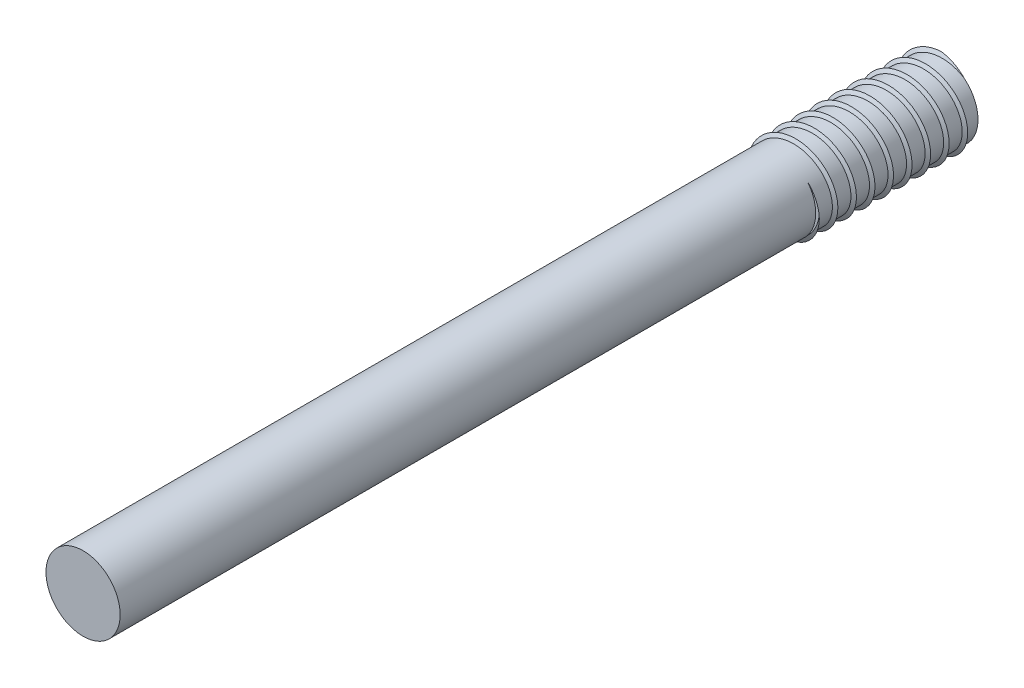
SolidWorks part; units mm, degrees
ref_plane "Front Plane" through (0, 0, 0) normal (0, 0, 1) x (1, 0, 0)
ref_plane "Top Plane" through (0, 0, 0) normal (0, 1, 0) x (1, 0, 0)
ref_plane "Right Plane" through (0, 0, 0) normal (1, 0, 0) x (0, 0, -1)
sketch "Sketch1" plane through (0, 0, 0) normal (0, 0, 1) x (1, 0, 0)
  line L0 (-5, 10) -> (-5, 0)
  line L1 (-5, -10) -> (5, -10)
  line L2 (-5, -10) -> (-5, 10)
  line L3 (-5, 10) -> (5, 10)
  line L4 (5, -10) -> (5, 10)
  line L5 (-5, -10) -> (5, 10) construction
  line L6 (-5, 10) -> (5, -10) construction
  circle A0 centre (0, 5) radius 2.5
  circle A1 centre (0, 5) radius 10
  point P0 (0, 0)
  dimension "D1" = 10
  dimension "D2" = 20
extrude "Boss-Extrude1" add sketch "Sketch1" along normal blind 5 contours L2 A1 L4 L3 L0 A0 | A1 L2 L1 L4 region at (0, 2.355, 0) region at (0, -7.2687, 0)
extrude "Boss-Extrude2" add sketch "Sketch1<3>" against normal blind 50 contours L4 A1 L2 L0 L3 | L2 A1 L4 L3 L0 A0 region at (0, 2.355, 0) region at (-5.2735, 5, 0)
sketch "Sketch1<3>" plane through (0, 0, 0) normal (0, 0, 1) x (1, 0, 0) same geometry as "Sketch1"
sketch "Sketch2" plane through (0, 0, -50) normal (0, 0, -1) x (-1, 0, 0)
  circle A0 centre (0, 5) radius 8
extrude "Cut-Extrude1" cut sketch "Sketch2" against normal blind 50
sketch "Sketch3" plane through (0, 0, -50) normal (0, 0, -1) x (-1, 0, 0)
  circle A0 centre (0, 5) radius 8
curve "Helix/Spiral1" pitch 4 height 140 radius 8 centre (0, 5, -50) axis (0, 0, 1) start towards (-1, 0, 0)
ref_plane "Plane1" through (0, 5, 0) normal (0, 1, 0) x (1, 0, 0)
sketch "Sketch4" plane through (0, 5, 0) normal (0, 1, 0) x (1, 0, 0)
  line L2 (-8.75, 50) -> (-8, 49.567)
  line L3 (-8, 49.567) -> (-8, 50.433)
  line L4 (-8, 50.433) -> (-8.75, 50)
  circle A0 centre (-8.25, 50) radius 0.25 construction
sweep "Cut-Sweep1" cut profiles "Sketch4" path "Helix/Spiral1" align with end faces yes
sketch "Sketch6" plane through (0, 10, 0) normal (0, 1, 0) x (1, 0, 0)
  line L1 (-5, -5) -> (5, -5)
  line L2 (-5, -5) -> (-5, 0)
  line L3 (-5, 0) -> (5, 0)
  line L4 (5, -5) -> (5, 0)
extrude "Cut-Extrude2" cut sketch "Sketch6" against normal blind 48
ref_plane "Plane2" through (0, 0, -45) normal (0, 0, -1) x (-1, 0, 0)
sketch "Sketch7" plane through (0, 0, -45) normal (0, 0, -1) x (-1, 0, 0)
  line L0 (0.8292, 14.2128) -> (1.3216, 14.9123)
  line L1 (0.4696, 14.989) -> (0.8292, 14.2128)
  line L2 (0, 14.25) -> (0.4277, 14.9908)
  line L4 (-0.4277, 14.9908) -> (0, 14.25)
  line L5 (0.433, 15) -> (0, 15) [skipped]
  line L6 (1.6517, 14.1013) -> (2.2048, 14.7539)
  line L7 (1.3631, 14.9067) -> (1.6517, 14.1013)
  line L8 (2.4608, 13.9167) -> (3.0702, 14.517)
  line L9 (2.2456, 14.7446) -> (2.4608, 13.9167)
  line L10 (3.2502, 13.6602) -> (3.911, 14.2035)
  line L11 (3.1101, 14.5041) -> (3.2502, 13.6602)
  line L12 (4.0134, 13.334) -> (4.7202, 13.8159)
  line L13 (3.9495, 14.187) -> (4.0134, 13.334)
  line L14 (4.7443, 12.9407) -> (5.4915, 13.3572)
  line L15 (4.7571, 13.796) -> (4.7443, 12.9407)
  line L16 (5.437, 12.4834) -> (6.2185, 12.8314)
  line L17 (5.5264, 13.3342) -> (5.437, 12.4834)
  line L18 (6.0859, 11.9659) -> (6.8955, 12.2424)
  line L19 (6.2513, 12.8052) -> (6.0859, 11.9659)
  line L20 (6.6859, 11.3923) -> (7.5169, 11.5951)
  line L21 (6.9257, 12.2135) -> (6.6859, 11.3923)
  line L22 (7.2319, 10.7673) -> (8.0778, 10.8948)
  line L23 (7.5445, 11.5636) -> (7.2319, 10.7673)
  line L24 (7.7198, 10.0958) -> (8.5737, 10.147)
  line L25 (8.1025, 10.8609) -> (7.7198, 10.0958)
  line L26 (8.1455, 9.3833) -> (9.0006, 9.3577)
  line L27 (8.5952, 10.111) -> (8.1455, 9.3833)
  line L28 (8.5056, 8.6355) -> (9.355, 8.5333)
  line L29 (9.0188, 9.32) -> (8.5056, 8.6355)
  line L30 (8.7973, 7.8584) -> (9.634, 7.6805)
  line L31 (9.3697, 8.4941) -> (8.7973, 7.8584)
  line L32 (9.0181, 7.0583) -> (9.8355, 6.8062)
  line L33 (9.6452, 7.6402) -> (9.0181, 7.0583)
  line L34 (9.1663, 6.2417) -> (9.9578, 5.9172)
  line L35 (9.843, 6.765) -> (9.1663, 6.2417)
  line L36 (9.2407, 5.415) -> (10, 5.0209)
  line L37 (9.9616, 5.8755) -> (9.2407, 5.415)
  line L38 (9.2407, 4.585) -> (9.9616, 4.1245)
  line L39 (10, 4.9791) -> (9.2407, 4.585)
  line L40 (9.1663, 3.7583) -> (9.843, 3.235)
  line L41 (9.9578, 4.0828) -> (9.1663, 3.7583)
  line L42 (9.0181, 2.9417) -> (9.6452, 2.3598)
  line L43 (9.8355, 3.1938) -> (9.0181, 2.9417)
  line L44 (8.7973, 2.1416) -> (9.3697, 1.5059)
  line L45 (9.634, 2.3195) -> (8.7973, 2.1416)
  line L46 (8.5056, 1.3645) -> (9.0188, 0.68)
  line L47 (9.355, 1.4667) -> (8.5056, 1.3645)
  line L48 (8.1455, 0.6167) -> (8.5952, -0.111)
  line L49 (9.0006, 0.6423) -> (8.1455, 0.6167)
  line L50 (7.7198, -0.0958) -> (8.1025, -0.8609)
  line L51 (8.5737, -0.147) -> (7.7198, -0.0958)
  line L52 (7.2319, -0.7673) -> (7.5445, -1.5636)
  line L53 (8.0778, -0.8948) -> (7.2319, -0.7673)
  line L54 (6.6859, -1.3923) -> (6.9257, -2.2135)
  line L55 (7.5169, -1.5951) -> (6.6859, -1.3923)
  line L56 (6.0859, -1.9659) -> (6.2513, -2.8052)
  line L57 (6.8955, -2.2424) -> (6.0859, -1.9659)
  line L58 (5.437, -2.4834) -> (5.5264, -3.3342)
  line L59 (6.2185, -2.8314) -> (5.437, -2.4834)
  line L60 (4.7443, -2.9407) -> (4.7571, -3.796)
  line L61 (5.4915, -3.3572) -> (4.7443, -2.9407)
  line L62 (4.0134, -3.334) -> (3.9495, -4.187)
  line L63 (4.7202, -3.8159) -> (4.0134, -3.334)
  line L64 (3.2502, -3.6602) -> (3.1101, -4.5041)
  line L65 (3.911, -4.2035) -> (3.2502, -3.6602)
  line L66 (2.4608, -3.9167) -> (2.2456, -4.7446)
  line L67 (3.0702, -4.517) -> (2.4608, -3.9167)
  line L68 (1.6517, -4.1013) -> (1.3631, -4.9067)
  line L69 (2.2048, -4.7539) -> (1.6517, -4.1013)
  line L70 (0.8292, -4.2128) -> (0.4696, -4.989)
  line L71 (1.3216, -4.9123) -> (0.8292, -4.2128)
  line L72 (0, -4.25) -> (-0.4277, -4.9908)
  line L73 (0.4277, -4.9908) -> (0, -4.25)
  line L74 (-0.8292, -4.2128) -> (-1.3216, -4.9123)
  line L75 (-0.4696, -4.989) -> (-0.8292, -4.2128)
  line L76 (-1.6517, -4.1013) -> (-2.2048, -4.7539)
  line L77 (-1.3631, -4.9067) -> (-1.6517, -4.1013)
  line L78 (-2.4608, -3.9167) -> (-3.0702, -4.517)
  line L79 (-2.2456, -4.7446) -> (-2.4608, -3.9167)
  line L80 (-3.2502, -3.6602) -> (-3.911, -4.2035)
  line L81 (-3.1101, -4.5041) -> (-3.2502, -3.6602)
  line L82 (-4.0134, -3.334) -> (-4.7202, -3.8159)
  line L83 (-3.9495, -4.187) -> (-4.0134, -3.334)
  line L84 (-4.7443, -2.9407) -> (-5.4915, -3.3572)
  line L85 (-4.7571, -3.796) -> (-4.7443, -2.9407)
  line L86 (-5.437, -2.4834) -> (-6.2185, -2.8314)
  line L87 (-5.5264, -3.3342) -> (-5.437, -2.4834)
  line L88 (-6.0859, -1.9659) -> (-6.8955, -2.2424)
  line L89 (-6.2513, -2.8052) -> (-6.0859, -1.9659)
  line L90 (-6.6859, -1.3923) -> (-7.5169, -1.5951)
  line L91 (-6.9257, -2.2135) -> (-6.6859, -1.3923)
  line L92 (-7.2319, -0.7673) -> (-8.0778, -0.8948)
  line L93 (-7.5445, -1.5636) -> (-7.2319, -0.7673)
  line L94 (-7.7198, -0.0958) -> (-8.5737, -0.147)
  line L95 (-8.1025, -0.8609) -> (-7.7198, -0.0958)
  line L96 (-8.1455, 0.6167) -> (-9.0006, 0.6423)
  line L97 (-8.5952, -0.111) -> (-8.1455, 0.6167)
  line L98 (-8.5056, 1.3645) -> (-9.355, 1.4667)
  line L99 (-9.0188, 0.68) -> (-8.5056, 1.3645)
  line L100 (-8.7973, 2.1416) -> (-9.634, 2.3195)
  line L101 (-9.3697, 1.5059) -> (-8.7973, 2.1416)
  line L102 (-9.0181, 2.9417) -> (-9.8355, 3.1938)
  line L103 (-9.6452, 2.3598) -> (-9.0181, 2.9417)
  line L104 (-9.1663, 3.7583) -> (-9.9578, 4.0828)
  line L105 (-9.843, 3.235) -> (-9.1663, 3.7583)
  line L106 (-9.2407, 4.585) -> (-10, 4.9791)
  line L107 (-9.9616, 4.1245) -> (-9.2407, 4.585)
  line L108 (-9.2407, 5.415) -> (-9.9616, 5.8755)
  line L109 (-10, 5.0209) -> (-9.2407, 5.415)
  line L110 (-9.1663, 6.2417) -> (-9.843, 6.765)
  line L111 (-9.9578, 5.9172) -> (-9.1663, 6.2417)
  line L112 (-9.0181, 7.0583) -> (-9.6452, 7.6402)
  line L113 (-9.8355, 6.8062) -> (-9.0181, 7.0583)
  line L114 (-8.7973, 7.8584) -> (-9.3697, 8.4941)
  line L115 (-9.634, 7.6805) -> (-8.7973, 7.8584)
  line L116 (-8.5056, 8.6355) -> (-9.0188, 9.32)
  line L117 (-9.355, 8.5333) -> (-8.5056, 8.6355)
  line L118 (-8.1455, 9.3833) -> (-8.5952, 10.111)
  line L119 (-9.0006, 9.3577) -> (-8.1455, 9.3833)
  line L120 (-7.7198, 10.0958) -> (-8.1025, 10.8609)
  line L121 (-8.5737, 10.147) -> (-7.7198, 10.0958)
  line L122 (-7.2319, 10.7673) -> (-7.5445, 11.5636)
  line L123 (-8.0778, 10.8948) -> (-7.2319, 10.7673)
  line L124 (-6.6859, 11.3923) -> (-6.9257, 12.2135)
  line L125 (-7.5169, 11.5951) -> (-6.6859, 11.3923)
  line L126 (-6.0859, 11.9659) -> (-6.2513, 12.8052)
  line L127 (-6.8955, 12.2424) -> (-6.0859, 11.9659)
  line L128 (-5.437, 12.4834) -> (-5.5264, 13.3342)
  line L129 (-6.2185, 12.8314) -> (-5.437, 12.4834)
  line L130 (-4.7443, 12.9407) -> (-4.7571, 13.796)
  line L131 (-5.4915, 13.3572) -> (-4.7443, 12.9407)
  line L132 (-4.0134, 13.334) -> (-3.9495, 14.187)
  line L133 (-4.7202, 13.8159) -> (-4.0134, 13.334)
  line L134 (-3.2502, 13.6602) -> (-3.1101, 14.5041)
  line L135 (-3.911, 14.2035) -> (-3.2502, 13.6602)
  line L136 (-2.4608, 13.9167) -> (-2.2456, 14.7446)
  line L137 (-3.0702, 14.517) -> (-2.4608, 13.9167)
  line L138 (-1.6517, 14.1013) -> (-1.3631, 14.9067)
  line L139 (-2.2048, 14.7539) -> (-1.6517, 14.1013)
  line L140 (-0.8292, 14.2128) -> (-0.4696, 14.989)
  line L141 (-1.3216, 14.9123) -> (-0.8292, 14.2128)
  circle A0 centre (0, 5) radius 10
  circle A1 centre (0, 5) radius 12.0427
  point P218 (0, 5)
  dimension "D1" = 70
extrude "Cut-Extrude3" cut sketch "Sketch7" against normal blind 10 contours L134 A0 L135 | L136 A0 L137 | L138 A0 L139 | L140 A0 L141 | L2 A0 L4 | L0 A0 L1 | L6 A0 L7 | L8 A0 L9 | L10 A0 L11 | L132 A0 L133 | L130 A0 L131 | L128 A0 L129 | L126 A0 L127 | L124 A0 L125 | L122 A0 L123 | L120 A0 L121 | L118 A0 L119 | L12 A0 L13 | L14 A0 L15 | L16 A0 L17 | L116 A0 L117 region at (-0.8738, 14.7087, -45) region at (-1.7406, 14.5913, -45) region at (0, 14.748, -45) region at (-2.5933, 14.3967, -45) region at (0.8738, 14.7087, -45) region at (-3.4252, 14.1264, -45) region at (1.7406, 14.5913, -45) region at (-4.2295, 13.7826, -45) region at (2.5933, 14.3967, -45) region at (-4.9997, 13.3681, -45) region at (3.4252, 14.1264, -45) region at (-5.7297, 12.8863, -45) region at (4.2295, 13.7826, -45) region at (4.9997, 13.3681, -45) region at (5.7297, 12.8863, -45) region at (6.4136, 12.3409, -45) region at (7.0458, 11.7365, -45) region at (7.6213, 11.0778, -45) region at (8.1354, 10.3701, -45) region at (8.584, 9.6193, -45) region at (8.9635, 8.8312, -45)
extrude "Cut-Extrude4" cut sketch "Sketch7<8>" against normal blind 10 contours L114 A0 L115 | L112 A0 L113 | L110 A0 L111 | L108 A0 L109 | L106 A0 L107 | L104 A0 L105 | L102 A0 L103 | L100 A0 L101 | L98 A0 L99 | L96 A0 L97 | L94 A0 L95 | L92 A0 L93 | L90 A0 L91 region at (9.2709, 8.0123, -45) region at (9.5036, 7.1691, -45) region at (9.6597, 6.3085, -45) region at (9.7381, 5.4373, -45) region at (9.7381, 4.5627, -45) region at (9.6597, 3.6915, -45) region at (9.5036, 2.8309, -45) region at (9.2709, 1.9877, -45) region at (8.9635, 1.1688, -45) region at (8.584, 0.3807, -45) region at (8.1354, -0.3701, -45) region at (7.6213, -1.0778, -45) region at (7.0458, -1.7365, -45)
sketch "Sketch7<8>" plane through (0, 0, -45) normal (0, 0, -1) x (-1, 0, 0) same geometry as "Sketch7"
extrude "Cut-Extrude5" cut sketch "Sketch7<11>" against normal blind 10 contours L88 A0 L89 | L86 A0 L87 | L84 A0 L85 | L82 A0 L83 | L80 A0 L81 | L78 A0 L79 | L76 A0 L77 | L74 A0 L75 | L72 A0 L73 | L70 A0 L71 | L68 A0 L69 | L66 A0 L67 | L64 A0 L65 | L62 A0 L63 | L60 A0 L61 region at (-4.9997, -3.3681, -45) region at (6.4136, -2.3409, -45) region at (-4.2295, -3.7826, -45) region at (5.7297, -2.8863, -45) region at (-3.4252, -4.1264, -45) region at (4.9997, -3.3681, -45) region at (-2.5933, -4.3967, -45) region at (4.2295, -3.7826, -45) region at (-1.7406, -4.5913, -45) region at (3.4252, -4.1264, -45) region at (-0.8738, -4.7087, -45) region at (2.5933, -4.3967, -45) region at (0, -4.748, -45) region at (1.7406, -4.5913, -45) region at (0.8738, -4.7087, -45)
sketch "Sketch7<11>" plane through (0, 0, -45) normal (0, 0, -1) x (-1, 0, 0) same geometry as "Sketch7"
extrude "Cut-Extrude6" cut sketch "Sketch7<12>" against normal blind 10 contours L58 A0 L59 | L56 A0 L57 | L54 A0 L55 | L52 A0 L53 | L50 A0 L51 | L48 A0 L49 | L46 A0 L47 | L44 A0 L45 | L42 A0 L43 | L40 A0 L41 | L38 A0 L39 | L36 A0 L37 | L34 A0 L35 | L32 A0 L33 | L30 A0 L31 | L28 A0 L29 | L26 A0 L27 | L24 A0 L25 | L22 A0 L23 | L20 A0 L21 | L18 A0 L19 region at (-6.4136, 12.3409, -45) region at (-7.0458, 11.7365, -45) region at (-7.6213, 11.0778, -45) region at (-8.1354, 10.3701, -45) region at (-8.584, 9.6193, -45) region at (-8.9635, 8.8312, -45) region at (-9.2709, 8.0123, -45) region at (-9.5036, 7.1691, -45) region at (-9.6597, 6.3085, -45) region at (-9.7381, 5.4373, -45) region at (-9.7381, 4.5627, -45) region at (-9.6597, 3.6915, -45) region at (-9.5036, 2.8309, -45) region at (-9.2709, 1.9877, -45) region at (-8.9635, 1.1688, -45) region at (-8.584, 0.3807, -45) region at (-8.1354, -0.3701, -45) region at (-7.6213, -1.0778, -45) region at (-7.0458, -1.7365, -45) region at (-6.4136, -2.3409, -45) region at (-5.7297, -2.8863, -45)
sketch "Sketch7<12>" plane through (0, 0, -45) normal (0, 0, -1) x (-1, 0, 0) same geometry as "Sketch7"
sketch "Sketch8" plane through (0, 0, -45) normal (0, 0, -1) x (-1, 0, 0)
  circle A0 centre (0, 5) radius 10
extrude "Cut-Extrude7" cut sketch "Sketch8" along normal through all and the other way blind 10
sketch "Sketch9" plane through (0, 0, -35) normal (0, 0, -1) x (-1, 0, 0)
  circle A0 centre (0, 5) radius 10
extrude "Boss-Extrude3" add sketch "Sketch9" against normal blind 35 separate body
combine bodies "Combine2" operation type subtract main body 111 bodies to subtract 110
sketch "Sketch11" plane through (0, 0, 0) normal (0, 0, 1) x (1, 0, 0)
  circle A0 centre (0, 5) radius 8
extrude "Boss-Extrude4" add sketch "Sketch11" along normal blind 150
